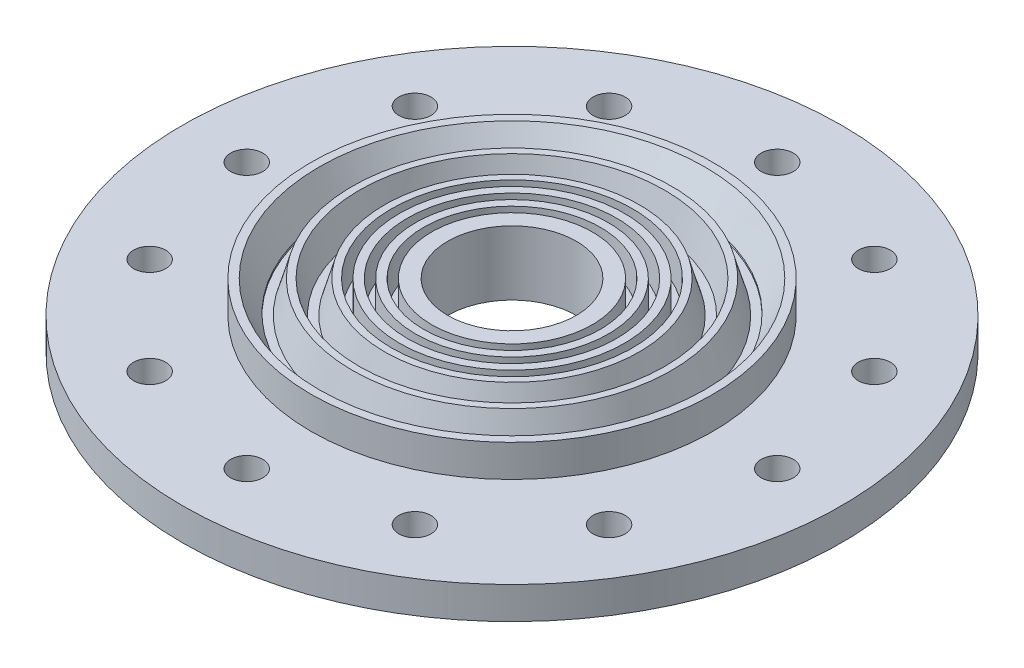
SolidWorks part; units mm, degrees
ref_plane "Front Plane" through (0, 0, 0) normal (0, 0, 1) x (1, 0, 0)
ref_plane "Top Plane" through (0, 0, 0) normal (0, 1, 0) x (1, 0, 0)
ref_plane "Right Plane" through (0, 0, 0) normal (1, 0, 0) x (0, 0, -1)
sketch "Sketch1" plane through (0, 0, 0) normal (0, 1, 0) x (1, 0, 0)
  line L0 (0, 15.875) -> (63.1218, 15.875)
  line L1 (0, 15.875) -> (0, 12.7)
  line L2 (0, -15.875) -> (0, -12.7)
  line L3 (0, 12.7) -> (63.8365, 12.7)
  line L4 (0, -12.7) -> (63.8365, -12.7)
  line L13 (0, -15.875) -> (63.1218, -15.875)
  circle A0 centre (0, 0) radius 39.6875
  circle A1 centre (0, 0) radius 30.1625
  circle A2 centre (0, 0) radius 31.75
  circle A3 centre (0, 0) radius 36.5125
  circle A4 centre (0, 0) radius 25.4
  circle A5 centre (0, 0) radius 23.8125
  circle A6 centre (0, 0) radius 15.875
  circle A7 centre (0, 0) radius 12.7
  circle A8 centre (0, 0) radius 65.0875
  circle A9 centre (0, 0) radius 22.225
  circle A10 centre (-26.1938, 45.3689) radius 3.175
  circle A11 centre (0, 52.3875) radius 3.175
  circle A12 centre (26.1937, 45.3689) radius 3.175
  circle A13 centre (45.3689, 26.1938) radius 3.175
  circle A14 centre (52.3875, 0) radius 3.175
  circle A15 centre (-45.3689, 26.1937) radius 3.175
  circle A16 centre (0, 0) radius 33.3375
  circle A17 centre (0, 0) radius 34.925
  circle A18 centre (0, 0) radius 28.575
  circle A19 centre (0, 0) radius 26.9875
  circle A20 centre (-52.3875, 0) radius 3.175
  circle A21 centre (-45.3689, -26.1938) radius 3.175
  circle A22 centre (-26.1937, -45.3689) radius 3.175
  circle A23 centre (0, -52.3875) radius 3.175
  circle A24 centre (26.1938, -45.3689) radius 3.175
  circle A25 centre (45.3689, -26.1937) radius 3.175
  circle A26 centre (0, 0) radius 20.6375
  circle A27 centre (0, 0) radius 19.05
  circle A28 centre (0, 0) radius 17.4625
extrude "Boss-Extrude2" add sketch "Sketch1" along normal blind 12.7 contours A3 L0 A0 L13 | A17 L0 A3 L13 | L0 A16 L13 A2 | L0 A2 L13 A1 | A18 L0 A1 L13 | L0 A19 L13 A4 | A5 L0 A4 L13 | A7 L1 A6 L2 | L3 A6 L1 | A7 L4 A6 L3 | L2 A6 L4 | A5 L13 A4 L4 | L13 A19 L4 A4 | A18 L13 A1 L4 | L13 A2 L4 A1 | L13 A16 L4 A2 | A17 L13 A3 L4 | A3 L13 A0 L4 | A3 L4 A0 L3 | A17 L4 A3 L3 | L4 A16 L3 A2 | L4 A2 L3 A1 | A18 L4 A1 L3 | L4 A19 L3 A4 | A5 L4 A4 L3 | A5 L3 A4 L0 | L3 A19 L0 A4 | A18 L3 A1 L0 | L3 A2 L0 A1 | L3 A16 L0 A2 | A17 L3 A3 L0 | A3 L3 A0 L0 region at (3.6248, 0, -13.9816) region at (-0.355, 0, -14.2875) region at (4.7625, 0, -12.4005) region at (3.6248, 0, 13.9816) region at (-24.4927, 0, 0) region at (19.9716, 0, -14.3177) region at (-26.1277, 0, 0) region at (21.904, 0, -14.3126) region at (21.0701, 0, -12.4406) region at (19.9716, 0, 14.3177) region at (22.9048, 0, -12.4411) region at (21.904, 0, 14.3126) region at (-29.3968, 0, 0) region at (25.6235, 0, -14.3058) region at (-31.031, 0, 0) region at (27.4309, 0, -14.3035) region at (26.4781, 0, -12.4419) region at (25.6235, 0, 14.3058) region at (-32.6649, 0, 0) region at (29.2124, 0, -14.3016) region at (28.2289, 0, -12.4422) region at (27.4309, 0, 14.3035) region at (29.9615, 0, -12.4425) region at (29.2124, 0, 14.3016) region at (-35.9324, 0, 0) region at (32.7147, 0, -14.2987) region at (-37.6119, 0, 0) region at (35.296, 0, -14.2972) region at (34.9369, 0, 0) region at (32.7147, 0, 14.2987) region at (37.3695, 0, 0) region at (35.296, 0, 14.2972)
chamfer "Chamfer1" distance 3.175 angle 62 1 edges at (0, 12.7, 34.925) first distance on face at (0, 12.7, 39.6875)
chamfer "Chamfer2" distance 6.35 angle 16 1 edges at (0, 12.7, 33.3375) first distance on face at (0, 12.7, 33.3375)
chamfer "Chamfer3" distance 1.5875 angle 76 1 edges at (0, 12.7, 28.575) first distance on face at (0, 12.7, 31.5167)
chamfer "Chamfer4" distance 6.35 angle 16 1 edges at (0, 12.7, 26.9875) first distance on face at (0, 12.7, 26.9875)
extrude "Boss-Extrude3" add sketch "Sketch1<20>" along normal blind 6.35 contours L0 A8 L13 A0 A25 A24 A23 A22 A21 A20 A15 A13 A12 A11 A10 | L13 A8 L4 A0 | L4 A8 L3 A0 A14 | L3 A8 L0 A0 | L0 A17 L13 A16 | A19 L0 A18 L13 | L13 A17 L4 A16 | L4 A17 L3 A16 | L3 A17 L0 A16 | A19 L3 A18 L0 | A19 L4 A18 L3 | A19 L13 A18 L4 | A9 L13 A5 L4 | A27 L13 A26 L4 | L13 A28 L4 A6 | L4 A28 L3 A6 | A27 L4 A26 L3 | A9 L4 A5 L3 | A9 L0 A5 L13 | A27 L0 A26 L13 | L0 A28 L13 A6 | A9 L3 A5 L0 | A27 L3 A26 L0 | L3 A28 L0 A6 region at (-16.303, 0, 0) region at (7.7398, 0, -14.5099) region at (7.7398, 0, 14.5099) region at (10.7552, 0, -12.4339) region at (-19.5836, 0, 0) region at (13.6102, 0, -14.3531) region at (15.233, 0, -12.438) region at (13.6102, 0, 14.3531) region at (-22.8571, 0, 0) region at (17.9686, 0, -14.3249) region at (19.1911, 0, -12.44) region at (17.9686, 0, 14.3249) region at (-27.7624, 0, 0) region at (23.784, 0, -14.3088) region at (24.7051, 0, -12.4416) region at (23.784, 0, 14.3088) region at (-34.2987, 0, 0) region at (30.9725, 0, -14.3) region at (31.6789, 0, -12.4427) region at (30.9725, 0, 14.3) region at (-41.5146, 0, 0) region at (50.2517, 0, -14.2926) region at (50.7185, 0, -12.3257) region at (50.2517, 0, 14.2926)
sketch "Sketch1<20>" plane through (0, 0, 0) normal (0, 1, 0) x (1, 0, 0) same geometry as "Sketch1"
extrude "Boss-Extrude4" add sketch "Sketch1<21>" along normal blind 12.7 contours A28 L4 A27 L3 | A26 L4 A9 L3 | A26 L13 A9 L4 | A28 L13 A27 L4 | A26 L0 A9 L13 | A28 L0 A27 L13 | A28 L3 A27 L0 | A26 L3 A9 L0 region at (-17.9448, 0, 0) region at (11.0831, 0, -14.3875) region at (13.0922, 0, -12.4364) region at (11.0831, 0, 14.3875) region at (-21.2209, 0, 0) region at (15.8658, 0, -14.3356) region at (17.253, 0, -12.4391) region at (15.8658, 0, 14.3356)
sketch "Sketch1<21>" plane through (0, 0, 0) normal (0, 1, 0) x (1, 0, 0) same geometry as "Sketch1"
